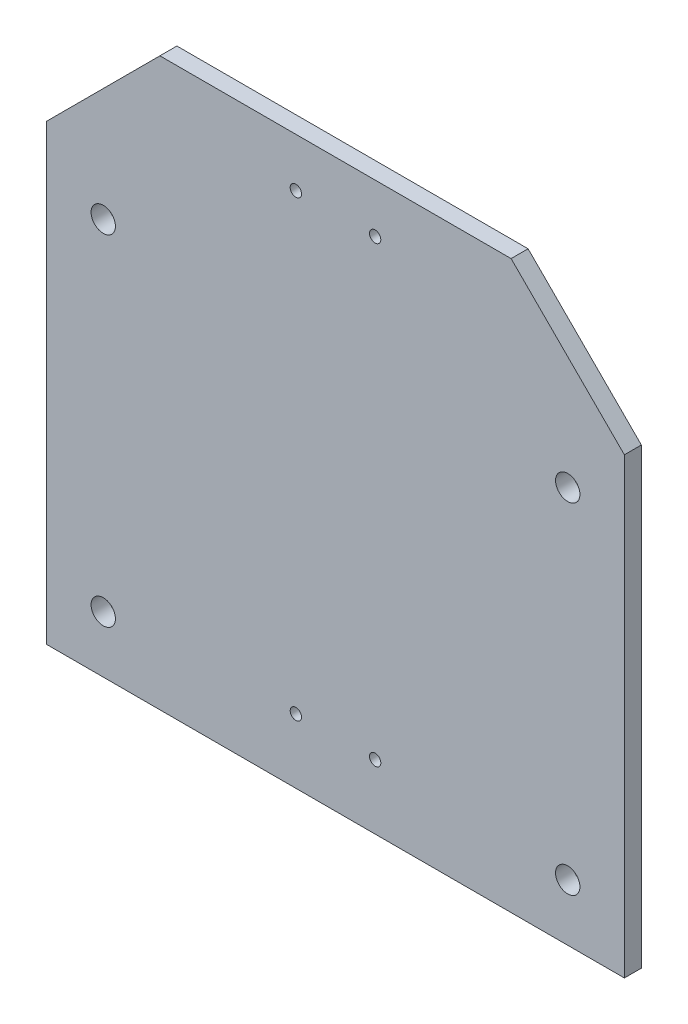
SolidWorks part; units mm, degrees
material "ABS"
ref_plane "前视基准面" through (0, 0, 0) normal (0, 0, 1) x (1, 0, 0)
ref_plane "上视基准面" through (0, 0, 0) normal (0, 1, 0) x (1, 0, 0)
ref_plane "右视基准面" through (0, 0, 0) normal (1, 0, 0) x (0, 0, -1)
sketch "草图1" plane through (0, 0, 0) normal (0, 0, 1) x (1, 0, 0)
  line L0 (-51.0025, -60.1275) -> (51.0025, -60.1275)
  line L1 (-51.0025, -141.1287) -> (-51.0025, 19.8725) construction
  line L2 (51.0025, 19.8725) -> (51.0025, -141.1287) construction
  line L3 (51.0025, -60.1275) -> (51.0025, 19.8725)
  line L4 (51.0025, 19.8725) -> (31.0025, 39.8725) construction
  line L5 (51.0025, 19.8725) -> (31.0025, 39.8725)
  line L6 (31.0025, 39.8725) -> (-31.0025, 39.8725)
  line L7 (-31.0025, 39.8725) -> (-51.0025, 19.8725)
  line L8 (-51.0025, 19.8725) -> (-51.0025, -60.1275)
  dimension "D1" = 100
extrude "凸台-拉伸1" add sketch "草图1" against normal blind 3
sketch "草图2" plane through (0, 0, 0) normal (0, 0, 1) x (1, 0, 0)
  circle A0 centre (-41.0025, 9.8725) radius 2.15
  circle A1 centre (-41.0025, -50.1275) radius 2.15
  circle A2 centre (41.0025, 9.8725) radius 2.15
  circle A3 centre (41.0025, -50.1275) radius 2.15
extrude "切除-拉伸1" cut sketch "草图2" against normal blind 3
sketch "草图3" plane through (0, 0, -3) normal (0, 0, -1) x (-1, 0, 0)
  circle A0 centre (-7.0002, 31.25) radius 1
  circle A1 centre (6.9998, 31.25) radius 1
  circle A2 centre (-7.0002, -48.75) radius 1
  circle A3 centre (6.9998, -48.75) radius 1
extrude "切除-拉伸2" cut sketch "草图3" against normal blind 70
